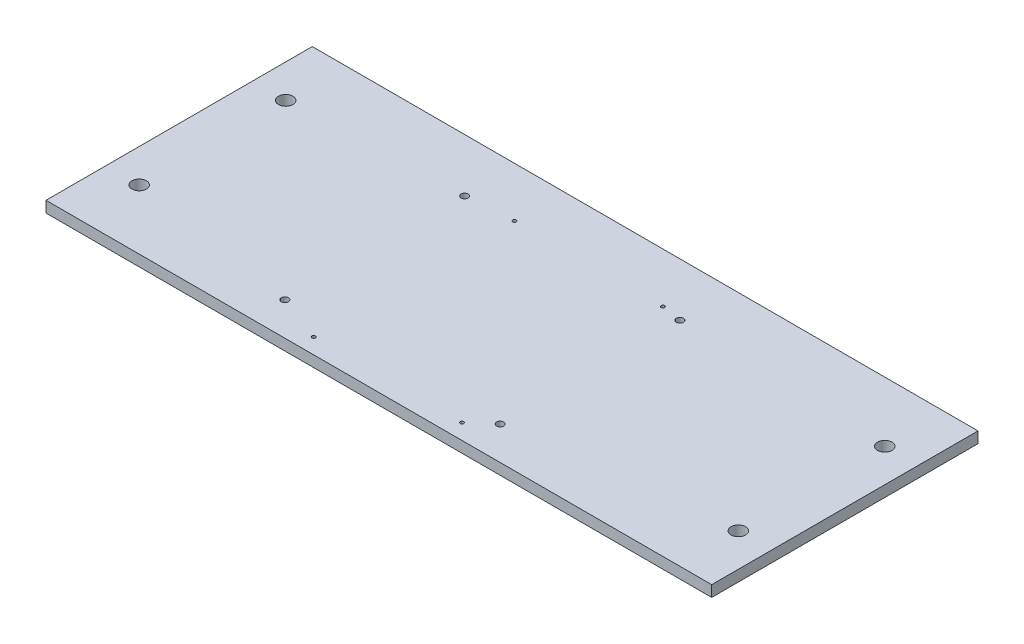
SolidWorks part; units mm, degrees
ref_plane "Front Plane" through (0, 0, 0) normal (0, 0, 1) x (1, 0, 0)
ref_plane "Top Plane" through (0, 0, 0) normal (0, 1, 0) x (1, 0, 0)
ref_plane "Right Plane" through (0, 0, 0) normal (1, 0, 0) x (0, 0, -1)
sketch "Sketch1" plane through (0, 0, 0) normal (0, 1, 0) x (1, 0, 0)
  line L1 (0, 0) -> (300, 0)
  line L2 (0, 0) -> (0, -120)
  line L3 (0, -120) -> (300, -120)
  line L4 (300, 0) -> (300, -120)
  dimension "D1" = 120
  dimension "D2" = 300
extrude "Boss-Extrude1" add sketch "Sketch1" along normal blind 5
sketch "Sketch2" plane through (0, 5, 0) normal (0, 1, 0) x (1, 0, 0)
  line L0 (150, 0) -> (150, -120) construction
  line L1 (300, 0) -> (0, 0) construction
  line L2 (0, -120) -> (300, -120) construction
  line L3 (0, -60) -> (300, -60) construction
  line L4 (0, 0) -> (0, -120) construction
  line L5 (300, -120) -> (300, 0) construction
  circle A0 centre (15, -27) radius 3.2639
  circle A1 centre (285, -27) radius 3.2639
  circle A2 centre (285, -93) radius 3.2639
  circle A3 centre (15, -93) radius 3.2639
  dimension "D1" = 6.5278
  dimension "D2" = 33
  dimension "D3" = 135
sketch "Sketch3" plane through (0, 5, 0) normal (0, 1, 0) x (1, 0, 0)
  line L0 (0, -120) -> (300, -120) construction
  line L1 (0, 0) -> (0, -120) construction
  line L4 (300, 0) -> (0, 0) construction
  point P0 (113.6419, -22.4976)
  point P1 (113.6419, -112.9946)
  point P2 (180.4745, -112.9946)
  point P3 (180.4745, -22.4976)
  dimension "D1" = 66.8326
  dimension "D2" = 90.497
  dimension "D3" = 7.0054
  dimension "D4" = 90.497
  dimension "D5" = 66.8326
  dimension "D6" = 113.6419
  dimension "D7" = 113.6419
  dimension "D8" = 22.4976
hole_wizard "Tap Drill for M2 Tap1" positions "Sketch4" profile "Sketch5" hole size "M2" standard "ISO" end condition through all
sketch "Sketch4" plane through (0, 5, 0) normal (0, 1, 0) x (1, 0, 0)
  point P0 (113.6419, -112.9946)
  point P3 (180.4745, -112.9946)
  point P6 (180.4745, -22.4976)
  point P9 (113.6419, -22.4976)
sketch "Sketch5" plane through (113.6419, 5, 112.9946) normal (1, 0, 0) x (0, 0, 1)
  line L0 (0, 0) -> (0, 5)
  line L1 (0, 5) -> (0.8, 5)
  line L2 (0.8, 5) -> (0.8, 0)
  line L5 (0.8, 0) -> (0, 0)
  line L11 (0, -6.35) -> (0, 107.95) construction
  dimension "Thru Hole Dia." = 1.6
  dimension "Thru Hole Depth" = 5
sketch "Sketch6" plane through (0, 5, 0) normal (0, 1, 0) x (1, 0, 0)
  line L1 (300, 0) -> (0, 0) construction
  line L2 (0, -120) -> (300, -120) construction
  point P0 (92.6419, -105)
  point P1 (189.6419, -105)
  point P2 (189.6419, -24)
  point P3 (92.6419, -24)
  dimension "D1" = 97
  dimension "D2" = 97
  dimension "D3" = 81
  dimension "D4" = 15
  dimension "D5" = 21
  dimension "D6" = 81
  dimension "D7" = 15
  dimension "D8" = 24
hole_wizard "M3 Clearance Hole1" positions "Sketch7" profile "Sketch8" hole size "M3" standard "ISO" end condition through all
sketch "Sketch7" plane through (0, 5, 0) normal (0, 1, 0) x (1, 0, 0)
  point P0 (92.6419, -105)
  point P3 (92.6419, -24)
  point P6 (189.6419, -24)
  point P9 (189.6419, -105)
sketch "Sketch8" plane through (92.6419, 5, 105) normal (1, 0, 0) x (0, 0, 1)
  line L0 (0, 0) -> (0, 5)
  line L1 (0, 5) -> (1.6, 5)
  line L2 (1.6, 5) -> (1.6, 0)
  line L5 (1.6, 0) -> (0, 0)
  line L11 (0, -6.35) -> (0, 107.95) construction
  dimension "Thru Hole Dia." = 3.2
  dimension "Thru Hole Depth" = 5
extrude "Cut-Extrude1" cut sketch "Sketch2" against normal through all contours A0 | A3 | A1 | A2
